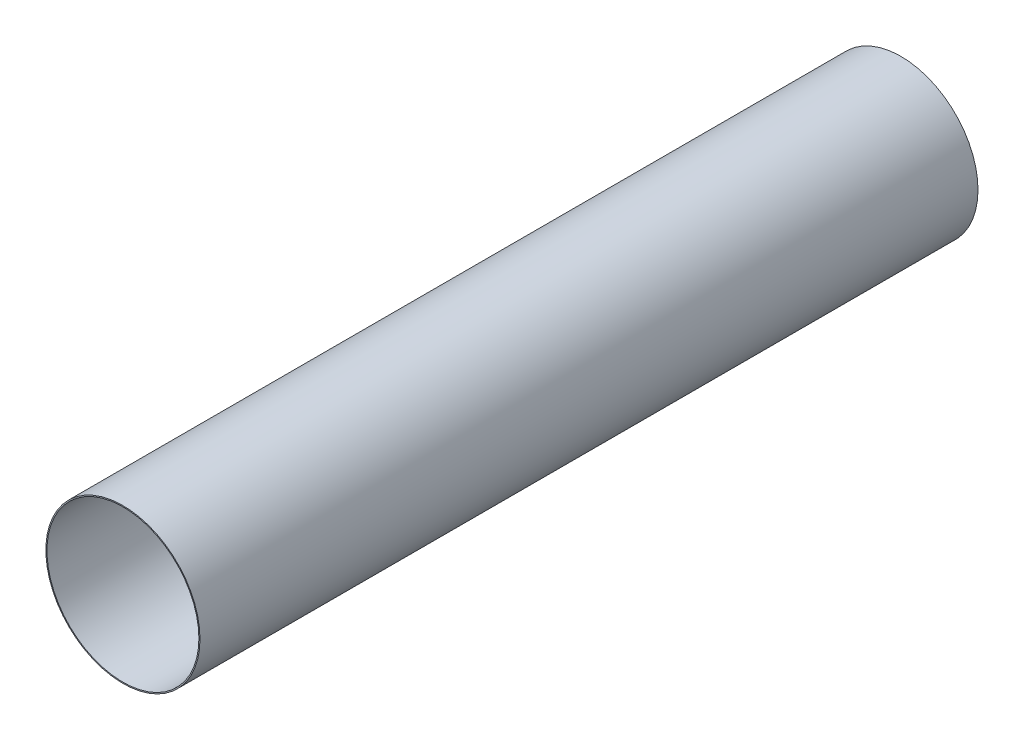
SolidWorks part; units mm, degrees
ref_plane "Front Plane" through (0, 0, 0) normal (0, 0, 1) x (1, 0, 0)
ref_plane "Top Plane" through (0, 0, 0) normal (0, 1, 0) x (1, 0, 0)
ref_plane "Right Plane" through (0, 0, 0) normal (1, 0, 0) x (0, 0, -1)
sketch "Sketch1" plane through (0, 0, 0) normal (0, 0, 1) x (1, 0, 0)
  circle A0 centre (0, 0) radius 79.375
  circle A1 centre (0, 0) radius 80.518
  dimension "D1" = 158.75
  dimension "D2" = 1.143
extrude "Boss-Extrude1" add sketch "Sketch1" along normal blind 812.8
